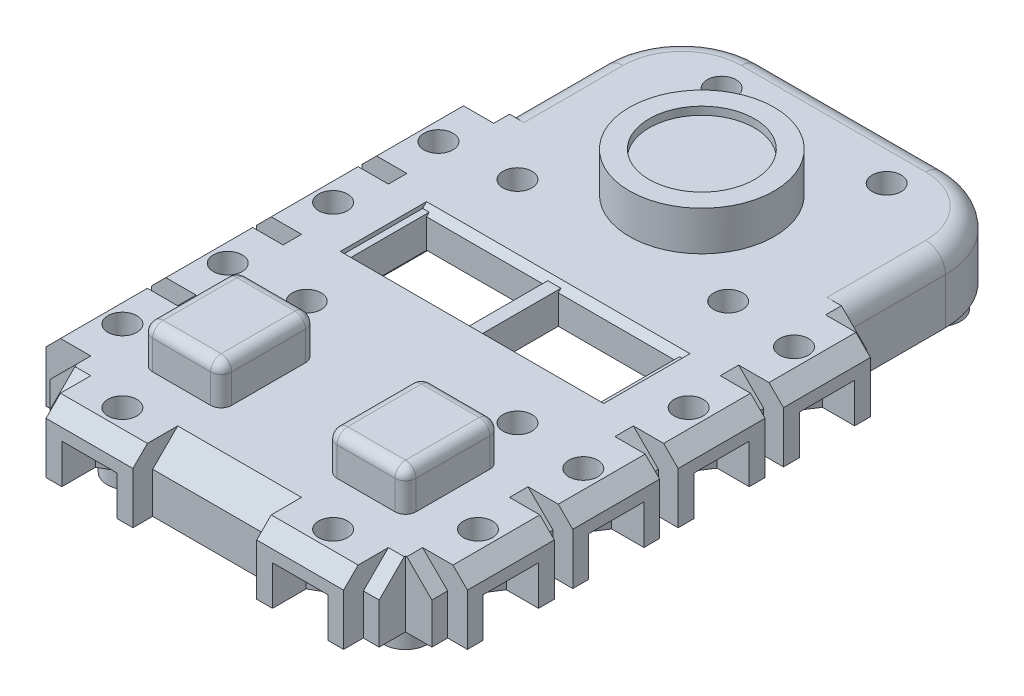
SolidWorks part; units mm, degrees
ref_plane "Front Plane" through (0, 0, 0) normal (0, 0, 1) x (1, 0, 0)
ref_plane "Top Plane" through (0, 0, 0) normal (0, 1, 0) x (1, 0, 0)
ref_plane "Right Plane" through (0, 0, 0) normal (1, 0, 0) x (0, 0, -1)
sketch "Sketch1" plane through (0, 0, 0) normal (0, 1, 0) x (1, 0, 0)
  line L0 (-55, 0) -> (55, 0) construction
  line L1 (-16, -25) -> (16, -25)
  line L2 (-16, -25) -> (-16, 25)
  line L3 (-16, 25) -> (16, 25)
  line L4 (16, -25) -> (16, 25)
  line L5 (0, -55) -> (0, 55) construction
  point P4 (16, 0)
  point P9 (0, 25)
  dimension "D1" = 32
  dimension "D2" = 50
extrude "Boss-Extrude1" add sketch "Sketch1" along normal mid plane 5
sketch "Sketch4" plane through (0, 2.5, 0) normal (0, 1, 0) x (1, 0, 0)
  line L0 (-13, 19) -> (-13, 11.5)
  line L1 (-13, 11.5) -> (-14.5, 11.5)
  line L2 (-14.5, 11.5) -> (-14.5, 10.3)
  line L3 (-14.5, 10.3) -> (-16, 10.3)
  line L4 (-16, 25) -> (-16, -25)
  line L5 (-16, -25) -> (16, -25)
  line L6 (16, -25) -> (16, 25)
  line L7 (16, 25) -> (-16, 25)
  line L8 (-16, 10.3) -> (-16, 3.7)
  line L9 (-11.3, -25) -> (-4.7, -25)
  line L12 (-16, 3.7) -> (-14.5, 3.7)
  line L13 (-14.5, 3.7) -> (-14.5, 2.3)
  line L14 (-14.5, 2.3) -> (-16, 2.3)
  line L15 (-16, 2.3) -> (-16, -4.3)
  line L16 (-16, -5.7) -> (-16, -12.3)
  line L17 (-16, -4.3) -> (-14.5, -4.3)
  line L19 (-16, -5.7) -> (-14.5, -5.7)
  line L20 (-14.5, -4.3) -> (-14.5, -5.7)
  line L21 (-16, 25) -> (-16, -25) construction
  line L22 (-16, -13.7) -> (-16, -20.3)
  line L23 (-16, -12.3) -> (-14.5, -12.3)
  line L25 (-16, -13.7) -> (-14.5, -13.7)
  line L26 (-14.5, -12.3) -> (-14.5, -13.7)
  line L27 (-16, -20.3) -> (-14.5, -20.3)
  line L28 (-14.5, -20.3) -> (-14.5, -21.5)
  line L29 (-14.5, -21.5) -> (-12.5, -21.5)
  line L30 (-12.5, -21.5) -> (-12.5, -23.5)
  line L31 (-12.5, -23.5) -> (-11.3, -23.5)
  line L32 (-11.3, -23.5) -> (-11.3, -25)
  line L35 (-4.7, -23.5) -> (-4.7, -25)
  line L38 (0, -2.75) -> (0, 2.75) construction
  line L41 (-20, 25) -> (-20, -26)
  line L42 (-20, -26) -> (0, -26)
  line L43 (0, -23.5) -> (0, -26)
  line L44 (-4.7, -23.5) -> (0, -23.5)
  line L45 (16, 25) -> (-16, 25) construction
  line L46 (-20, 25) -> (-7, 25)
  arc A0 (-7, 25) -> (-13, 19) centre (-7, 19) ccw
  dimension "D6" = 6
  dimension "D2" = 6.6
  dimension "D3" = 1.2
  dimension "D4" = 1.4
  dimension "D5" = 1.5
  dimension "D7" = 1.5
  dimension "D8" = 4.7
  dimension "D9" = 13
  dimension "D10" = 20
  dimension "D11" = 13.5
  dimension "D12" = 51
  dimension "D1" = 0
extrude "Cut-Extrude1" cut sketch "Sketch4" against normal blind 10
mirror "Mirror1" about plane through (0, 0, 0) normal (1, 0, 0) of "Cut-Extrude1"
sketch "Sketch5" plane through (0, 2.5, 0) normal (0, 1, 0) x (1, 0, 0)
  line L0 (-16, 10.3) -> (-16, 3.7) construction
  line L1 (-14.5, 3.7) -> (-16, 3.7) construction
  line L2 (-11.3, -25) -> (-4.7, -25) construction
  line L3 (0, -2.75) -> (0, 2.75) construction
  circle A0 centre (-13.5, 7) radius 1.1
  circle A1 centre (13.5, 7) radius 1.1
  circle A2 centre (13.5, -1) radius 1.1
  circle A3 centre (13.5, -9) radius 1.1
  circle A4 centre (13.5, -17) radius 1.1
  circle A5 centre (-13.5, -1) radius 1.1
  circle A6 centre (-13.5, -9) radius 1.1
  circle A7 centre (-13.5, -17) radius 1.1
  circle A8 centre (-8, -22.5) radius 1.1
  circle A9 centre (8, -22.5) radius 1.1
  dimension "D3" = 2.2
  dimension "D1" = 2.5
  dimension "D2" = 3.3
  dimension "D6" = 8
  dimension "D7" = 27
  dimension "D8" = 16
  dimension "D9" = 2.5
  dimension "D10" = 8
  dimension "D4" = 2
  dimension "D5" = 4
extrude "Cut-Extrude2" cut sketch "Sketch5" against normal blind 10
chamfer "Chamfer1" distance 1.1 angle 45 10 edges at (8, 2.5, 25) (16, 2.5, -7) (16, 2.5, 1) (16, 2.5, 9) (16, 2.5, 17) (-8, 2.5, 25) (-16, 2.5, 17) (-16, 2.5, 9) (-16, 2.5, 1) (-16, 2.5, -7)
fillet "Fillet1" radius 1.5 5 edges at (13, 2.5, -15.25) (11.2426, 2.5, -23.2426) (0, 2.5, -25) (-11.2426, 2.5, -23.2426) (-13, 2.5, -15.25)
chamfer "Chamfer2" distance 1.9 angle 45 13 edges at (-14.5, 2.5, -3) (-14.5, 2.5, 13) (-14.5, 2.5, 5) (-14.5, 2.5, -10.9) (14.5, 2.5, -10.9) (14.5, 2.5, -3) (14.5, 2.5, 5) (14.5, 2.5, 13) (11.9, 2.5, 23.5) (0, 2.5, 23.5) (-11.9, 2.5, 23.5) (14.5, 2.5, 20.9) (-14.5, 2.5, 20.9)
sketch "Sketch6" plane through (0, 2.5, 0) normal (0, 1, 0) x (1, 0, 0)
  line L0 (-6.265, 21.27) -> (6.265, 21.27) construction
  line L1 (0, -2.75) -> (0, 2.75) construction
  line L2 (-7, 25) -> (7, 25) construction
  line L3 (-8, 7.5) -> (8, 7.5) construction
  line L4 (-8, 7.5) -> (-8, -8.5) construction
  line L5 (-8, -8.5) -> (8, -8.5) construction
  line L6 (8, 7.5) -> (8, -8.5) construction
  circle A0 centre (-6.265, 21.27) radius 1.1
  circle A1 centre (6.265, 21.27) radius 1.1
  circle A6 centre (6.265, 11.27) radius 1.1 [skipped]
  circle A7 centre (6.265, 1.27) radius 1.1 [skipped]
  circle A8 centre (-6.265, 11.27) radius 1.1 [skipped]
  circle A9 centre (-6.265, 1.27) radius 1.1 [skipped]
  circle A10 centre (-8, 7.5) radius 1.1
  circle A11 centre (8, 7.5) radius 1.1
  circle A12 centre (8, -8.5) radius 1.1
  circle A13 centre (-8, -8.5) radius 1.1
  point P3 (0, 21.27)
  point P8 (0, 7.5)
  dimension "D1" = 2.2
  dimension "D4" = 12.53
  dimension "D5" = 13.77
  dimension "D6" = 16
  dimension "D7" = 3.73
  dimension "D2" = 2
  dimension "D3" = 3
extrude "Cut-Extrude3" cut sketch "Sketch6" against normal blind 4
sketch "Sketch7" plane through (0, 2.5, 0) normal (0, 1, 0) x (1, 0, 0)
  line L0 (0, -2.75) -> (0, 2.75) construction
  line L1 (-10, -11.8) -> (-4, -11.8)
  line L2 (-10, -11.8) -> (-10, -19)
  line L3 (-10, -19) -> (-4, -19)
  line L4 (-4, -11.8) -> (-4, -19)
  line L5 (4, -11.8) -> (10, -11.8)
  line L6 (4, -11.8) -> (4, -19)
  line L7 (4, -19) -> (10, -19)
  line L8 (10, -11.8) -> (10, -19)
  line L9 (-4.7, -25) -> (-11.3, -25) construction
  dimension "D1" = 6
  dimension "D2" = 7.2
  dimension "D3" = 4
  dimension "D4" = 4
  dimension "D5" = 6
extrude "Boss-Extrude2" add sketch "Sketch7" along normal blind 3
fillet "Fillet2" radius 0.8 16 edges at (7, 5.5, 11.8) (10, 5.5, 15.4) (7, 5.5, 19) (4, 5.5, 15.4) (-7, 5.5, 11.8) (-4, 5.5, 15.4) (-7, 5.5, 19) (-10, 5.5, 15.4) (10, 4, 11.8) (-4, 4, 11.8) (-4, 4, 19) (10, 4, 19) (4, 4, 19) (4, 4, 11.8) (-10, 4, 11.8) (-10, 4, 19)
sketch "Sketch8" plane through (0, 2.5, 0) normal (0, 1, 0) x (1, 0, 0)
  line L0 (0, -4.4) -> (0, 4.4) construction
  line L1 (-7, 25) -> (7, 25) construction
  circle A0 centre (0, 13.5) radius 5.5
  dimension "D1" = 11
  dimension "D2" = 11.5
extrude "Boss-Extrude3" add sketch "Sketch8" along normal blind 3
sketch "Sketch9" plane through (0, 5.5, 0) normal (0, 1, 0) x (1, 0, 0)
  circle A0 centre (0, 13.5) radius 4
  circle A1 centre (0, 13.5) radius 5.5 construction
  dimension "D1" = 8
extrude "Cut-Extrude4" cut sketch "Sketch9" against normal blind 0.6
sketch "Sketch10" plane through (0, 2.5, 0) normal (0, 1, 0) x (1, 0, 0)
  line L0 (-7, 25) -> (7, 25) construction
  line L1 (-9.5, 1.4) -> (-0.5, 1.4)
  line L2 (-9.5, 1.4) -> (-9.5, -2.75)
  line L3 (-9.5, -2.75) -> (-0.5, -2.75)
  line L4 (-0.5, 1.4) -> (-0.5, -2.75)
  line L5 (9.5, 1.4) -> (0.5, 1.4)
  line L6 (9.5, 1.4) -> (9.5, -2.75)
  line L7 (9.5, -2.75) -> (0.5, -2.75)
  line L8 (0.5, 1.4) -> (0.5, -2.75)
  dimension "D1" = 4.15
  dimension "D2" = 9
  dimension "D3" = 1
  dimension "D4" = 0.5
  dimension "D5" = 23.6
extrude "Cut-Extrude5" cut sketch "Sketch10" against normal through all
sketch "Sketch11" plane through (0, 2.5, 0) normal (0, 1, 0) x (1, 0, 0)
  line L0 (-9.5, 1.4) -> (-9.5, -2.75) construction
  line L1 (-10, 1.4) -> (10, 1.4)
  line L2 (-10, 1.4) -> (-10, -2.75)
  line L3 (-10, -2.75) -> (10, -2.75)
  line L4 (10, 1.4) -> (10, -2.75)
  line L5 (9.5, -2.75) -> (9.5, 1.4) construction
  line L6 (-0.5, 1.4) -> (-9.5, 1.4) construction
  line L7 (-9.5, -2.75) -> (-0.5, -2.75) construction
  dimension "D1" = 0.5
  dimension "D2" = 0.5
extrude "Cut-Extrude6" cut sketch "Sketch11" against normal blind 0.3
chamfer "Chamfer3" distance 1.2 angle 45 2 edges at (0, 2.5, 2.75) (0, 2.5, -1.4)
ref_plane "Plane1" through (0, 0.5, 0) normal (0, 1, 0) x (1, 0, 0)
sketch "Sketch12" plane through (0, 0.5, 0) normal (0, 1, 0) x (1, 0, 0)
  line L1 (-12.2876, 9.1) -> (-14.7124, 9.1)
  line L2 (-14.7124, 9.1) -> (-15.9249, 7) construction
  line L3 (-15.9249, 7) -> (-14.7124, 4.9) construction
  line L4 (-14.7124, 4.9) -> (-12.2876, 4.9)
  line L5 (-12.2876, 4.9) -> (-11.0751, 7)
  line L6 (-11.0751, 7) -> (-12.2876, 9.1)
  line L49 (-14.7124, 9.1) -> (-17.7124, 9.1)
  line L50 (-14.7124, 9.1) -> (-14.7124, 4.9) construction
  line L51 (-14.7124, 4.9) -> (-17.7124, 4.9)
  line L52 (-17.7124, 9.1) -> (-17.7124, 4.9)
  circle A0 centre (-13.5, 7) radius 2.1 construction
  circle A1 centre (-13.5, 7) radius 1.1 construction
  dimension "D1" = 4.2
  dimension "D2" = 3
extrude "Cut-Extrude7" cut sketch "Sketch12" against normal blind 1.5
sketch "Sketch13" plane through (0, -2.5, 0) normal (0, -1, 0) x (1, 0, 0)
  line L0 (-16, -4.9) -> (-13.4423, -4.9)
  line L1 (-13.4423, -4.9) -> (-12.5474, -6.45)
  line L2 (-16, -9.1) -> (-13.5577, -9.1)
  line L3 (-13.5577, -9.1) -> (-12.579, -7.6015)
  line L4 (-16, -4.9) -> (-16, -9.1)
  line L5 (-16, -4.9) -> (-12.2876, -4.9) construction
  line L6 (-16, -9.1) -> (-16, -4.9) construction
  line L7 (-12.2876, -4.9) -> (-11.0751, -7) construction
  circle A0 centre (-13.5, -7) radius 1.1 construction
  arc A1 (-12.579, -7.6015) -> (-12.5474, -6.45) centre (-13.5, -7) ccw
  point P8 (-16, -7)
extrude "Cut-Extrude8" cut sketch "Sketch13" against normal up to next
pattern_linear "LPattern1" count 4 spacing 8 along (0, 0, 1) of "Cut-Extrude7", "Cut-Extrude8"
sketch "Sketch14" plane through (0, 0.5, 0) normal (0, 1, 0) x (1, 0, 0)
  line L1 (-8, -24.9249) -> (-5.9, -23.7124) construction
  line L2 (-5.9, -23.7124) -> (-5.9, -21.2876)
  line L3 (-5.9, -21.2876) -> (-8, -20.0751)
  line L4 (-8, -20.0751) -> (-10.1, -21.2876)
  line L5 (-10.1, -21.2876) -> (-10.1, -23.7124)
  line L6 (-10.1, -23.7124) -> (-8, -24.9249) construction
  line L7 (-10.1, -23.7124) -> (-5.9, -23.7124) construction
  line L8 (-10.1, -23.7124) -> (-10.1, -26.7124)
  line L9 (-10.1, -26.7124) -> (-5.9, -26.7124)
  line L10 (-5.9, -23.7124) -> (-5.9, -26.7124)
  circle A0 centre (-8, -22.5) radius 2.1 construction
  circle A1 centre (-8, -22.5) radius 1.1 construction
  dimension "D1" = 4.2
  dimension "D2" = 3
extrude "Cut-Extrude9" cut sketch "Sketch14" against normal blind 1.55
sketch "Sketch15" plane through (0, -2.5, 0) normal (0, -1, 0) x (1, 0, 0)
  line L0 (-10.1, 25) -> (-5.9, 25)
  line L1 (-5.9, 25) -> (-5.9, 22.4423)
  line L2 (-5.9, 22.4423) -> (-7.45, 21.5474)
  line L3 (-10.1, 25) -> (-10.1, 22.4423)
  line L4 (-10.1, 22.4423) -> (-8.55, 21.5474)
  line L5 (-5.9, 25) -> (-5.9, 21.2876) construction
  line L6 (-5.9, 21.2876) -> (-8, 20.0751) construction
  line L8 (-11.3, 25) -> (-4.7, 25) construction
  circle A0 centre (-8, 22.5) radius 1.1 construction
  arc A1 (-8.55, 21.5474) -> (-7.45, 21.5474) centre (-8, 22.5) ccw
  point P7 (-8, 25)
extrude "Cut-Extrude10" cut sketch "Sketch15" against normal up to next
mirror "Mirror2" about plane through (0, 0, 0) normal (1, 0, 0) of "Cut-Extrude8", "LPattern1", "Cut-Extrude9", "Cut-Extrude10", "Cut-Extrude7"
sketch "Sketch16" plane through (0, -2.5, 0) normal (0, -1, 0) x (1, 0, 0)
  line L0 (7, -25) -> (-7, -25) construction
  line L1 (-11.74, 19.1) -> (11.74, 19.1)
  line L2 (-11.74, 19.1) -> (-11.74, -17.74)
  line L3 (-5.74, -23.74) -> (5.74, -23.74)
  line L4 (11.74, 19.1) -> (11.74, -17.74)
  line L5 (-13, -19) -> (-13, -11.5) construction
  line L6 (-4.7, 23.5) -> (4.7, 23.5) construction
  arc A0 (11.74, -17.74) -> (5.74, -23.74) centre (5.74, -17.74) cw
  arc A1 (-5.74, -23.74) -> (-11.74, -17.74) centre (-5.74, -17.74) cw
  arc A2 (7, -25) -> (13, -19) centre (7, -19) ccw construction
  circle A3 centre (-8, 8.5) radius 1.715
  circle A4 centre (8, 8.5) radius 1.715
  circle A5 centre (-6.265, -21.27) radius 1.715
  circle A6 centre (6.265, -21.27) radius 1.715
  circle A7 centre (8, -7.5) radius 1.715
  circle A8 centre (-8, -7.5) radius 1.715
  circle A9 centre (8, 8.5) radius 1.1 construction
  circle A10 centre (-8, 8.5) radius 1.1 construction
  circle A11 centre (8, -7.5) radius 1.1 construction
  circle A12 centre (-8, -7.5) radius 1.1 construction
  circle A13 centre (-6.265, -21.27) radius 1.1 construction
  circle A14 centre (6.265, -21.27) radius 1.1 construction
  point P11 (0, -23.74)
  dimension "D1" = 1.26
  dimension "D4" = 3.43
  dimension "D2" = 1.26
  dimension "D3" = 4.4
extrude "Cut-Extrude11" cut sketch "Sketch16" against normal blind 4.5
sketch "Sketch17" plane through (0, 2, 0) normal (0, -1, 0) x (1, 0, 0)
  circle A0 centre (0, -13.5) radius 3.25
  circle A1 centre (0, -13.5) radius 5.5 construction
  dimension "D1" = 6.5
extrude "Boss-Extrude4" add sketch "Sketch17" along normal blind 3
sketch "Sketch18" plane through (0, 2, 0) normal (0, -1, 0) x (1, 0, 0)
  line L8 (8.7, 13.1) -> (8.7, 17.7)
  line L9 (5.3, 13.1) -> (8.7, 13.1)
  line L10 (5.3, 17.7) -> (5.3, 13.1)
  line L11 (8.7, 17.7) -> (5.3, 17.7)
  line L12 (8.7, 13.1) -> (8.7, 17.7)
  line L13 (5.3, 13.1) -> (8.7, 13.1)
  line L14 (5.3, 17.7) -> (5.3, 13.1)
  line L15 (8.7, 17.7) -> (5.3, 17.7)
  line L20 (-5.3, 13.1) -> (-5.3, 17.7)
  line L21 (-8.7, 13.1) -> (-5.3, 13.1)
  line L22 (-8.7, 17.7) -> (-8.7, 13.1)
  line L23 (-5.3, 17.7) -> (-8.7, 17.7)
  line L24 (-5.3, 13.1) -> (-5.3, 17.7)
  line L25 (-8.7, 13.1) -> (-5.3, 13.1)
  line L26 (-8.7, 17.7) -> (-8.7, 13.1)
  line L27 (-5.3, 17.7) -> (-8.7, 17.7)
  dimension "D1" = 0.5
  dimension "D2" = 0.5
extrude "Cut-Extrude12" cut sketch "Sketch18" against normal offset from surface (3 mm away) 0.5 up to face at (7, 5.5, 15.4)
sketch "Sketch20" plane through (0, 2, 0) normal (0, -1, 0) x (1, 0, 0)
  line L0 (-4.7, 23.5) -> (4.7, 23.5) construction
  circle A0 centre (0, 13.6) radius 3.35
  circle A1 centre (0, 13.6) radius 2.4
  dimension "D1" = 6.7
  dimension "D2" = 4.8
  dimension "D3" = 9.9
extrude "Boss-Extrude5" add sketch "Sketch20" along normal blind 3
sketch "Sketch21" plane through (0, 2, 0) normal (0, -1, 0) x (1, 0, 0)
  line L0 (0.5, 3.45) -> (9.5, 3.45) construction
  line L1 (-10.5, 4.85) -> (10.5, 4.85)
  line L2 (-10.5, 4.85) -> (-10.5, -3.5)
  line L3 (-10.5, -3.5) -> (10.5, -3.5)
  line L4 (10.5, 4.85) -> (10.5, -3.5)
  line L5 (9.5, -2.1) -> (9.5, 3.45) construction
  line L6 (0.5, 3.45) -> (0.5, -2.1) construction
  line L7 (9.5, -2.1) -> (0.5, -2.1) construction
  line L8 (-0.5, -2.1) -> (-9.5, -2.1) construction
  line L9 (-9.5, 3.45) -> (-9.5, -2.1) construction
  line L10 (-9.5, 3.45) -> (-0.5, 3.45) construction
  line L11 (-0.5, -2.1) -> (-0.5, 3.45) construction
  line L12 (0.5, 3.45) -> (9.5, 3.45)
  line L13 (9.5, -2.1) -> (9.5, 3.45)
  line L14 (0.5, 3.45) -> (0.5, -2.1)
  line L15 (9.5, -2.1) -> (0.5, -2.1)
  line L16 (-0.5, -2.1) -> (-9.5, -2.1)
  line L17 (-9.5, 3.45) -> (-9.5, -2.1)
  line L18 (-9.5, 3.45) -> (-0.5, 3.45)
  line L19 (-0.5, -2.1) -> (-0.5, 3.45)
  dimension "D1" = 1.4
  dimension "D2" = 1.4
  dimension "D3" = 1
  dimension "D4" = 1
extrude "Boss-Extrude6" add sketch "Sketch21" along normal blind 2.2
sketch "Sketch22" plane through (0, 2, 0) normal (0, -1, 0) x (1, 0, 0)
  line L0 (7, -25) -> (-7, -25) construction
  line L1 (-10.5, 19.5) -> (10.5, 19.5) construction
  line L3 (-9.5, -22) -> (9.5, -22) construction
  circle A0 centre (-10.5, 19.5) radius 1.65
  circle A1 centre (10.5, 19.5) radius 1.65
  circle A2 centre (9.5, -22) radius 1.65
  circle A3 centre (-9.5, -22) radius 1.65
  point P8 (0, -22)
  point P10 (0, 19.5)
  dimension "D5" = 3.3
  dimension "D1" = 21
  dimension "D2" = 19
  dimension "D3" = 3
  dimension "D4" = 41.5
extrude "Boss-Extrude7" add sketch "Sketch22" along normal offset from surface (6.5 mm away) 2 up to face at (0, -2.5, -7.8742) offset beyond the face yes
sketch "Sketch23" plane through (0, -4.5, 0) normal (0, -1, 0) x (1, 0, 0)
  circle A0 centre (10.5, 19.5) radius 1.15
  circle A1 centre (-10.5, 19.5) radius 1.15
  circle A2 centre (9.5, -22) radius 1.15
  circle A3 centre (-9.5, -22) radius 1.15
  circle A4 centre (-9.5, -22) radius 1.65 construction
  arc A5 (10.7931, -20.9751) -> (7.9774, -21.3642) centre (9.5, -22) ccw construction
  circle A6 centre (-10.5, 19.5) radius 1.65 construction
  circle A7 centre (10.5, 19.5) radius 1.65 construction
  dimension "D1" = 2.3
extrude "Cut-Extrude13" cut sketch "Sketch23" against normal blind 5
sketch "Sketch24" plane through (0, -2.5, 0) normal (0, -1, 0) x (1, 0, 0)
  line L1 (-12.34, 19.7) -> (-12.1378, 19.7)
  line L2 (-12.34, 19.7) -> (-12.34, -18.34)
  line L3 (-6.34, -24.34) -> (6.34, -24.34)
  line L4 (12.34, 19.7) -> (12.34, -18.34)
  line L5 (5.74, -23.74) -> (-5.74, -23.74)
  line L6 (11.74, -17.74) -> (11.74, 18.4115)
  line L8 (-11.74, -17.74) -> (-11.74, 18.4115)
  line L9 (-5.74, -23.74) -> (5.74, -23.74) construction
  line L10 (-11.74, 18.4115) -> (-11.74, -17.74) construction
  line L11 (11.74, -17.74) -> (11.74, 18.4115) construction
  line L13 (12.1378, 19.7) -> (12.34, 19.7)
  arc A0 (-5.74, -23.74) -> (-11.74, -17.74) centre (-5.74, -17.74) cw
  arc A1 (-6.34, -24.34) -> (-12.34, -18.34) centre (-6.34, -18.34) cw
  arc A2 (11.74, -17.74) -> (5.74, -23.74) centre (5.74, -17.74) cw
  arc A3 (6.34, -24.34) -> (12.34, -18.34) centre (6.34, -18.34) ccw
  arc A4 (11.74, 18.4115) -> (8.8992, 19.1) centre (10.5, 19.5) ccw construction
  arc A5 (11.74, 18.4115) -> (12.1378, 19.7) centre (10.5, 19.5) ccw
  arc A8 (-12.1378, 19.7) -> (-11.74, 18.4115) centre (-10.5, 19.5) ccw
  dimension "D5" = 6
  dimension "D6" = 6
  dimension "D7" = 6
  dimension "D8" = 6
  dimension "D1" = 0.6
  dimension "D3" = 0.6
  dimension "D4" = 0.6
